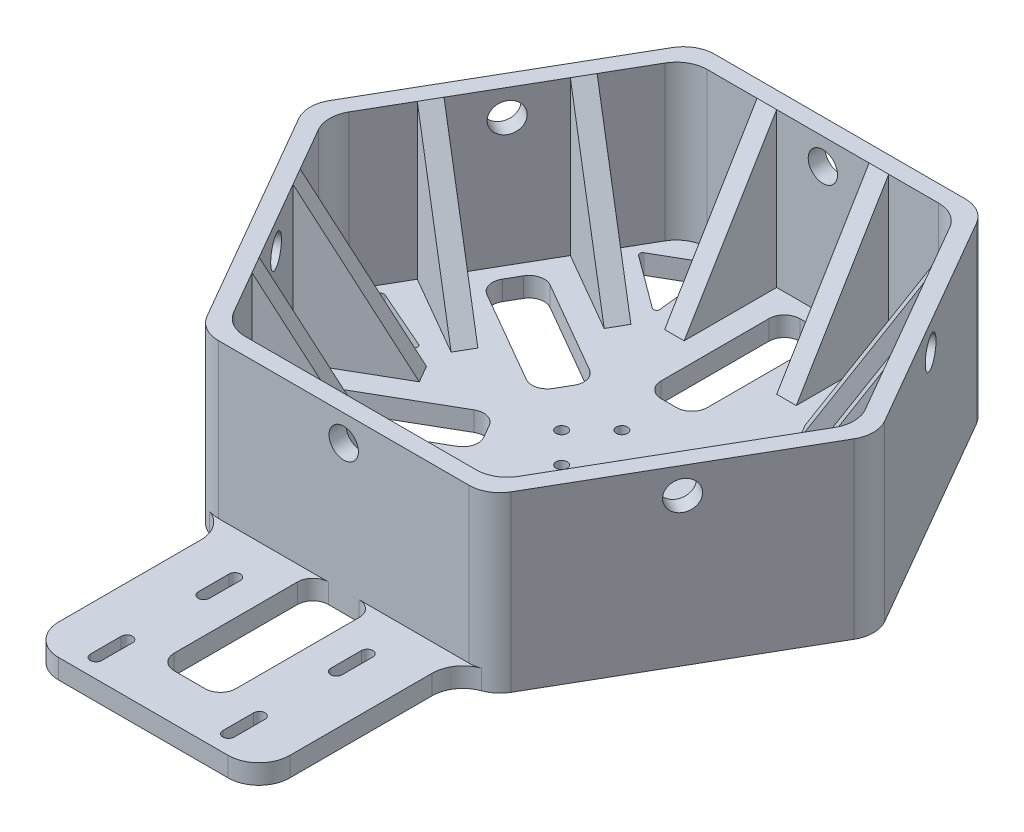
SolidWorks part; units mm, degrees
ref_plane "Front" through (0, 0, 0) normal (0, 0, 1) x (1, 0, 0)
ref_plane "Top" through (0, 0, 0) normal (0, 1, 0) x (1, 0, 0)
ref_plane "Right" through (0, 0, 0) normal (1, 0, 0) x (0, 0, -1)
sketch "Esquisse1" plane through (0, 0, 0) normal (0, 1, 0) x (1, 0, 0)
  line L0 (-50, 0) -> (50, 0) construction
  line L1 (43.3, -74.9978) -> (86.6, 0)
  line L2 (86.6, 0) -> (43.3, 74.9978)
  line L3 (43.3, 74.9978) -> (-43.3, 74.9978)
  line L4 (-43.3, 74.9978) -> (-86.6, 0)
  line L5 (-86.6, 0) -> (-43.3, -74.9978)
  line L6 (-43.3, -74.9978) -> (43.3, -74.9978)
  line L7 (46.475, -80.4971) -> (92.95, 0)
  line L8 (92.95, 0) -> (46.475, 80.4971)
  line L9 (46.475, 80.4971) -> (-46.475, 80.4971)
  line L10 (-46.475, 80.4971) -> (-92.95, 0)
  line L11 (-92.95, 0) -> (-46.475, -80.4971)
  line L12 (-46.475, -80.4971) -> (46.475, -80.4971)
  line L13 (86.6, 0) -> (92.95, 0) construction
  circle A0 centre (0, 0) radius 74.9978 construction
  circle A1 centre (0, 0) radius 80.4971 construction
  point P18 (43.3, -74.9978)
  dimension "D1" = 86.6
  dimension "D2" = 6.35
extrude "Boss.-Extru.1" add sketch "Esquisse1" along normal blind 50
sketch "Esquisse2" plane through (0, 0, 0) normal (0, -1, 0) x (1, 0, 0)
  line L0 (46.475, 80.4971) -> (92.95, 0) construction
  line L1 (92.95, 0) -> (46.475, -80.4971) construction
  line L2 (46.475, -80.4971) -> (-46.475, -80.4971) construction
  line L3 (-46.475, -80.4971) -> (-92.95, 0) construction
  line L4 (-92.95, 0) -> (-46.475, 80.4971) construction
  line L5 (-46.475, 80.4971) -> (46.475, 80.4971) construction
  line L6 (46.475, 80.4971) -> (92.95, 0)
  line L7 (92.95, 0) -> (46.475, -80.4971)
  line L8 (46.475, -80.4971) -> (-46.475, -80.4971)
  line L9 (-46.475, -80.4971) -> (-92.95, 0)
  line L10 (-92.95, 0) -> (-46.475, 80.4971)
  line L11 (-46.475, 80.4971) -> (46.475, 80.4971)
extrude "Boss.-Extru.2" add sketch "Esquisse2" along normal blind 6.35
ref_plane "Plan1" through (18.18, 0, 0) normal (1, 0, 0) x (0, 0, -1)
sketch "Esquisse5" plane through (18.18, 0, 0) normal (1, 0, 0) x (0, 0, -1)
  line L0 (-74.9978, 50) -> (-44.9969, 0)
  line L5 (0, 0) -> (-74.9978, 0) construction
  point P2 (-74.9978, 50)
  point P5 (-59.5948, 0)
  point P7 (-44.9978, 0)
  point P8 (-74.9978, 66.0858)
  dimension "D1" = 58.31
rib "Nervure2" sketch "Esquisse5" sketch "Esquisse5" thickness 6.35 extrusion direction parallel to sketch draft on no parameters "D1"=6.35
mirror "Symétrie1" about plane through (0, 0, 0) normal (1, 0, 0) of "Nervure2"
ref_axis "Axe1" through (0, 133.9439, 0) along (0, -1, 0)
pattern_circular "Répétition circulaire1" count 6 every 60 about axis through (0, 133.9439, 0) along (0, -1, 0) of "Symétrie1", "Nervure2"
fillet "Congé1" radius 10 12 edges at (-92.95, 21.825, 0) (-46.475, 21.825, -80.4971) (-46.475, 21.825, 80.4971) (46.475, 21.825, 80.4971) (92.95, 21.825, 0) (46.475, 21.825, -80.4971) (43.3, 25, -74.9978) (86.6, 25, 0) (43.3, 25, 74.9978) (-43.3, 25, -74.9978) (-86.6, 25, 0) (-43.3, 25, 74.9978)
sketch "Esquisse6" plane through (0, 0, 80.4971) normal (0, 0, 1) x (1, 0, 0)
  line L0 (-40.7015, 50) -> (40.7015, 50) construction
  line L7 (0, -50) -> (0, 50) construction
  circle A0 centre (0, 41.5) radius 4.7625
  dimension "D1" = 9.525
  dimension "D2" = 8.5
extrude "Enlèv. mat.-Extru.1" cut sketch "Esquisse6" against normal up to next
pattern_circular "Répétition circulaire2" count 6 every 60 about axis through (0, 133.9439, 0) along (0, -1, 0) of "Enlèv. mat.-Extru.1"
sketch "Esquisse7" plane through (0, 0, 80.4971) normal (0, 0, 1) x (1, 0, 0)
  line L0 (40.7015, -6.35) -> (-40.7015, -6.35) construction
  line L1 (-37.5, 0) -> (37.5, 0)
  line L2 (-37.5, 0) -> (-37.5, -6.35)
  line L3 (-37.5, -6.35) -> (37.5, -6.35)
  line L4 (37.5, 0) -> (37.5, -6.35)
  line L5 (0, -50) -> (0, 50) construction
  point P8 (0, 0)
  dimension "D1" = 6.35
  dimension "D2" = 75
extrude "Boss.-Extru.3" add sketch "Esquisse7" along normal blind 65
fillet "Congé2" radius 10 4 edges at (-37.5, -3.175, 80.4971) (37.5, -3.175, 80.4971) (-37.5, -3.175, 145.4971) (37.5, -3.175, 145.4971)
sketch "Esquisse9" plane through (0, 0, 0) normal (0, 1, 0) x (1, 0, 0)
  line L8 (-23.335, -94.3771) -> (-19.665, -94.3771) construction
  line L10 (-23.335, -94.3771) -> (-23.335, -104.3771)
  line L12 (-19.665, -94.3771) -> (-19.665, -104.3771)
  line L13 (-19.665, -104.3771) -> (-23.335, -104.3771) construction
  line L14 (40.7015, -80.4971) -> (-40.7015, -80.4971) construction
  line L15 (0, -50) -> (0, 50) construction
  arc A8 (-19.665, -94.3771) -> (-23.335, -94.3771) centre (-21.5, -94.3771) ccw
  arc A9 (-19.665, -104.3771) -> (-23.335, -104.3771) centre (-21.5, -104.3771) cw
  point P8 (-18.5294, -94.3771)
  point P10 (-18.1127, -91.6889)
  dimension "D1" = 3.67
  dimension "D2" = 10
  dimension "D3" = 13.88
  dimension "D4" = 21.5
extrude "Enlèv. mat.-Extru.2" cut sketch "Esquisse9" against normal blind 68.65
pattern_linear "Répétition linéaire1" count 2 spacing 35 along (0, 0, 1) of "Enlèv. mat.-Extru.2"
mirror "Symétrie2" about plane through (0, 0, 0) normal (1, 0, 0) of "Répétition linéaire1"
sketch "Esquisse10" plane through (0, 0, 0) normal (0, 1, 0) x (1, 0, 0)
  line L0 (0, -50) -> (0, 50) construction
  circle A0 centre (0, 9.78) radius 1.83
  dimension "D1" = 3.66
  dimension "D2" = 9.78
extrude "Enlèv. mat.-Extru.3" cut sketch "Esquisse10" against normal up to next
pattern_circular "Répétition circulaire3" count 4 every 90 about axis through (0, 133.9439, 0) along (0, -1, 0) of "Enlèv. mat.-Extru.3"
sketch "Esquisse11" plane through (0, 0, 0) normal (0, 1, 0) x (1, 0, 0)
  line L1 (-10, -80.4971) -> (10, -80.4971)
  line L2 (-10, -80.4971) -> (-10, -130.4971)
  line L3 (-10, -130.4971) -> (10, -130.4971)
  line L4 (10, -80.4971) -> (10, -130.4971)
  line L6 (40.7015, -80.4971) -> (-40.7015, -80.4971) construction
  line L9 (27.5, -145.4971) -> (-27.5, -145.4971) construction
  point P6 (0, -130.4971)
  point P9 (0, -145.4971)
  dimension "D1" = 20
  dimension "D2" = 50
extrude "Enlèv. mat.-Extru.4" cut sketch "Esquisse11" against normal up to next contours L2 L3 L4 L1
fillet "Congé3" radius 5 4 edges at (10, -3.175, 130.4971) (10, -3.175, 80.4971) (-10, -3.175, 80.4971) (-10, -3.175, 130.4971)
sketch "Esquisse12" plane through (0, 0, 0) normal (0, 1, 0) x (1, 0, 0)
  line L0 (0, -50) -> (0, 50) construction
  line L1 (-7.5, -25) -> (7.5, -25)
  line L2 (-7.5, -25) -> (-7.5, -70)
  line L3 (-7.5, -70) -> (7.5, -70)
  line L4 (7.5, -25) -> (7.5, -70)
  point P4 (0, -25)
  point P7 (7.5, -20.7182)
  dimension "D1" = 45
  dimension "D2" = 15
  dimension "D3" = 25
extrude "Enlèv. mat.-Extru.5" cut sketch "Esquisse12" against normal up to next
fillet "Congé4" radius 5 4 edges at (7.5, -3.175, 70) (-7.5, -3.175, 70) (7.5, -3.175, 25) (-7.5, -3.175, 25)
pattern_circular "Répétition circulaire4" count 6 every 60 about axis through (0, 133.9439, 0) along (0, -1, 0) of "Congé4", "Enlèv. mat.-Extru.5"
sketch "Esquisse13" plane through (0, 0, 0) normal (0, 1, 0) x (1, 0, 0)
  line L0 (55, 0) -> (77.9129, -10)
  line L1 (77.9129, -10) -> (77.9129, 10)
  line L2 (77.9129, 10) -> (55, 0)
  line L3 (55, 0) -> (77.9129, 0) construction
  line L4 (-50, 0) -> (50, 0) construction
  dimension "D1" = 20
  dimension "D2" = 25
  dimension "D3" = 55
extrude "Enlèv. mat.-Extru.6" cut sketch "Esquisse13" against normal up to next
fillet "Congé5" radius 1 3 edges at (77.9129, -3.175, 10) (77.9129, -3.175, -10) (55, -3.175, 0)
pattern_circular "Répétition circulaire5" count 6 every 60 about axis through (0, 133.9439, 0) along (0, -1, 0) of "Congé5", "Enlèv. mat.-Extru.6"
